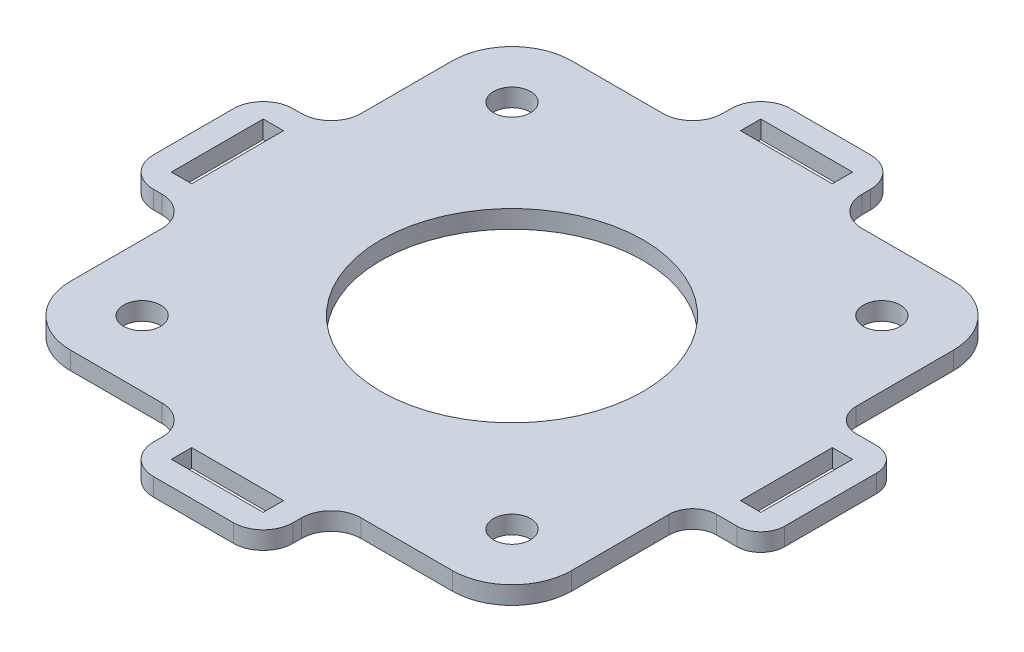
SolidWorks part; units mm, degrees
material "AISI 304"
ref_plane "Front Plane" through (0, 0, 0) normal (0, 0, 1) x (1, 0, 0)
ref_plane "Top Plane" through (0, 0, 0) normal (0, 1, 0) x (1, 0, 0)
ref_plane "Right Plane" through (0, 0, 0) normal (1, 0, 0) x (0, 0, -1)
sketch "Sketch1" plane through (0, 0, 0) normal (0, 1, 0) x (1, 0, 0)
  line L0 (0, 0) -> (0, 33.6449) construction
  line L5 (0, 0) -> (35.5051, 0) construction
  line L6 (3.85, -23) -> (3.85, -24.7)
  line L40 (23, 3.85) -> (24.7, 3.85)
  line L41 (23, 3.85) -> (23, -3.85)
  line L62 (23, -3.85) -> (24.7, -3.85)
  line L63 (24.7, 3.85) -> (24.7, -3.85)
  line L64 (23, 3.85) -> (24.7, -3.85) construction
  line L65 (23, -3.85) -> (24.7, 3.85) construction
  line L66 (21, 5.85) -> (26.7, 5.85)
  line L68 (21, -5.85) -> (26.7, -5.85)
  line L69 (26.7, 5.85) -> (26.7, -5.85)
  line L70 (21, 21) -> (5.85, 21)
  line L71 (21, 21) -> (21, 5.85)
  line L72 (21, -21) -> (5.85, -21)
  line L73 (-21, 21) -> (-21, 5.85)
  line L74 (21, 21) -> (-21, -21) construction
  line L75 (21, -21) -> (-21, 21) construction
  line L76 (3.85, -23) -> (-3.85, -23)
  line L77 (-3.85, -23) -> (-3.85, -24.7)
  line L78 (3.85, -24.7) -> (-3.85, -24.7)
  line L79 (5.85, -26.7) -> (-5.85, -26.7)
  line L80 (3.85, -23) -> (-3.85, -24.7) construction
  line L81 (-3.85, -23) -> (3.85, -24.7) construction
  line L82 (5.85, -21) -> (5.85, -26.7)
  line L83 (-5.85, -21) -> (-5.85, -26.7)
  line L84 (-23, -3.85) -> (-24.7, -3.85)
  line L85 (-23, -3.85) -> (-23, 3.85)
  line L86 (-23, 3.85) -> (-24.7, 3.85)
  line L87 (-24.7, -3.85) -> (-24.7, 3.85)
  line L88 (-26.7, -5.85) -> (-26.7, 5.85)
  line L89 (-23, -3.85) -> (-24.7, 3.85) construction
  line L90 (-23, 3.85) -> (-24.7, -3.85) construction
  line L91 (-21, -5.85) -> (-26.7, -5.85)
  line L92 (-21, 5.85) -> (-26.7, 5.85)
  line L93 (-3.85, 23) -> (-3.85, 24.7)
  line L94 (-3.85, 23) -> (3.85, 23)
  line L95 (3.85, 23) -> (3.85, 24.7)
  line L96 (-3.85, 24.7) -> (3.85, 24.7)
  line L97 (-5.85, 26.7) -> (5.85, 26.7)
  line L98 (-3.85, 23) -> (3.85, 24.7) construction
  line L99 (3.85, 23) -> (-3.85, 24.7) construction
  line L100 (-5.85, 21) -> (-5.85, 26.7)
  line L101 (5.85, 21) -> (5.85, 26.7)
  line L102 (-5.85, -21) -> (-21, -21)
  line L103 (-5.85, 21) -> (-21, 21)
  line L104 (-21, -5.85) -> (-21, -21)
  line L105 (21, -5.85) -> (21, -21)
  circle A1 centre (-15.5, 15.5) radius 1.55
  circle A2 centre (15.5, 15.5) radius 1.55
  circle A3 centre (15.5, -15.5) radius 1.55
  circle A4 centre (-15.5, -15.5) radius 1.55
  circle A5 centre (0, 0) radius 11
  point P0 (0, 0)
  point P3 (23.85, 0)
  point P25 (0, -23.85)
  point P37 (-23.85, 0)
  point P46 (0, 23.85)
  point P55 (0, 0)
  point P66 (0, 0)
  point P84 (0, 0)
  dimension "D1" = 42
  dimension "D2" = 3.1
  dimension "D8" = 2
  dimension "D15" = 22
  dimension "D9" = 15.5
  dimension "D3" = 2
  dimension "D4" = 2
  dimension "D5" = 42
  dimension "D10" = 2
  dimension "D11" = 1.7
  dimension "D12" = 7.7
  dimension "D13" = 4
  dimension "D14" = 15.5
  dimension "D6" = 2
  dimension "D7" = 2
extrude "Boss-Extrude1" add sketch "Sketch1" along normal blind 1.5
fillet "Fillet2" radius 5 4 edges at (21, 0.75, 21) (-21, 0.75, 21) (-21, 0.75, -21) (21, 0.75, -21)
fillet "Fillet3" radius 2 4 edges at (26.7, 0.75, -5.85) (21, 0.75, -5.85) (21, 0.75, 5.85) (26.7, 0.75, 5.85)
fillet "Fillet1" radius 2.5 12 edges at (-21, 0.75, -5.85) (-26.7, 0.75, -5.85) (-21, 0.75, 5.85) (-26.7, 0.75, 5.85) (-5.85, 0.75, 26.7) (-5.85, 0.75, 21) (5.85, 0.75, 26.7) (5.85, 0.75, 21) (5.85, 0.75, -21) (5.85, 0.75, -26.7) (-5.85, 0.75, -26.7) (-5.85, 0.75, -21)
